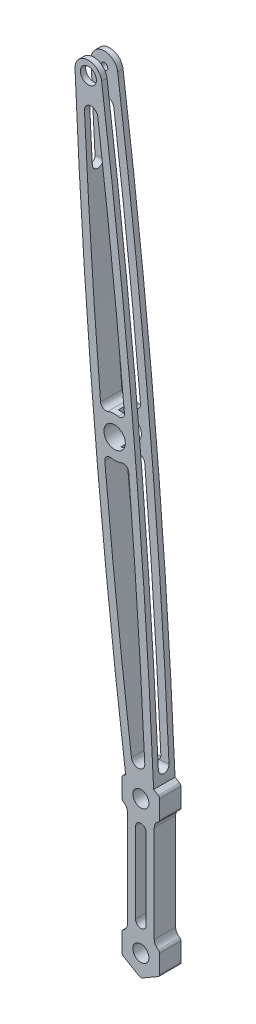
SolidWorks part; units mm, degrees
material "A2017"
ref_plane "正面" through (0, 0, 0) normal (0, 0, 1) x (1, 0, 0)
ref_plane "平面" through (0, 0, 0) normal (0, 1, 0) x (1, 0, 0)
ref_plane "右側面" through (0, 0, 0) normal (1, 0, 0) x (0, 0, -1)
sketch "ｽｹｯﾁ1" plane through (0, 0, 0) normal (0, 0, 1) x (1, 0, 0)
  line L0 (0, 0) -> (9.0749, 0) construction
  line L1 (0, 25) -> (0, 0) construction
  line L2 (0, -16.9171) -> (7, -20.9585)
  line L3 (7, 20.9585) -> (7, 29.0415)
  line L4 (7, 29.0415) -> (0, 33.0829)
  line L5 (0, 33.0829) -> (-7, 29.0415)
  line L6 (-7, 29.0415) -> (-7, 20.9585)
  line L7 (-7, 20.9585) -> (0, 16.9171)
  line L8 (0, 16.9171) -> (7, 20.9585)
  line L9 (-7, -20.9585) -> (0, -16.9171)
  line L10 (-7, -29.0415) -> (-7, -20.9585)
  line L11 (0, -33.0829) -> (-7, -29.0415)
  line L12 (7, -29.0415) -> (0, -33.0829)
  line L13 (7, -20.9585) -> (7, -29.0415)
  circle A0 centre (0, 25) radius 3
  circle A1 centre (0, -25) radius 3
  circle A2 centre (0, 25) radius 7 construction
  circle A3 centre (0, -25) radius 7 construction
  dimension "D1" = 6
  dimension "D2" = 50
  dimension "D3" = 14
extrude "ﾎﾞｽ - 押し出し1" add sketch "ｽｹｯﾁ1" along normal mid plane 8
sketch "ｽｹｯﾁ2" plane through (0, 0, 4) normal (0, 0, 1) x (1, 0, 0)
  line L0 (-7, 20.9585) -> (0, 16.9171) construction
  line L1 (5, -19.8038) -> (-5, -19.8038)
  line L2 (5, -19.8038) -> (5, 19.8038)
  line L3 (5, 19.8038) -> (-5, 19.8038)
  line L4 (-5, -19.8038) -> (-5, 19.8038)
  line L5 (5, -19.8038) -> (-5, 19.8038) construction
  line L6 (5, 19.8038) -> (-5, -19.8038) construction
  point P0 (0, 0)
  dimension "D1" = 10
extrude "ﾎﾞｽ - 押し出し2" add sketch "ｽｹｯﾁ2" against normal up to surface (8 mm away) up to face at (0, 25, -4)
fillet "ﾌｨﾚｯﾄ1" radius 3 4 edges at (5, -19.8038, 0) (-5, 19.8038, 0) (-5, -19.8038, 0) (5, 19.8038, 0)
fillet "ﾌｨﾚｯﾄ2" radius 1 10 edges at (-7, 20.9585, 0) (-7, 29.0415, 0) (0, 33.0829, 0) (7, 29.0415, 0) (7, 20.9585, 0) (7, -29.0415, 0) (0, -33.0829, 0) (-7, -29.0415, 0) (-7, -20.9585, 0) (7, -20.9585, 0)
sketch "ｽｹｯﾁ3" plane through (0, 0, -4) normal (0, 0, -1) x (-1, 0, 0)
  line L0 (0, -15) -> (0, 15) construction
  line L1 (-2, -15) -> (-2, 15)
  line L2 (2, -15) -> (2, 15)
  arc A0 (-2, -15) -> (2, -15) centre (0, -15) ccw
  arc A1 (2, 15) -> (-2, 15) centre (0, 15) ccw
  point P2 (0, 0)
  dimension "D1" = 4
  dimension "D2" = 30
extrude "ｶｯﾄ - 押し出し1" cut sketch "ｽｹｯﾁ3" against normal up to surface (8 mm away) up to face at (0, 0, 4)
sketch "ｽｹｯﾁ5" plane through (0, 0, 4) normal (0, 0, 1) x (1, 0, 0)
  circle A0 centre (0, -25) radius 3 construction
  circle A1 centre (0, 25) radius 3 construction
  circle A2 centre (0, -25) radius 3
  circle A3 centre (0, 25) radius 3
extrude "ﾎﾞｽ - 押し出し3" [suppressed] add sketch "ｽｹｯﾁ5" against normal blind 5
sketch "ｽｹｯﾁ8" plane through (0, 0, -4) normal (0, 0, -1) x (-1, 0, 0)
  circle A0 centre (0, -25) radius 3 construction
  circle A1 centre (0, 25) radius 3 construction
  circle A2 centre (0, -25) radius 3
  circle A3 centre (0, 25) radius 3
extrude "ﾎﾞｽ - 押し出し4" add sketch "ｽｹｯﾁ8" against normal blind 2.5
hole_wizard "M3 すきま穴1" positions "ｽｹｯﾁ6" profile "ｽｹｯﾁ7" hole size "M3" standard "JIS" end condition through all
sketch "ｽｹｯﾁ6" plane through (0, 0, 4) normal (0, 0, -1) x (-1, 0, 0)
  point P0 (0, 25)
  point P3 (0, -25)
sketch "ｽｹｯﾁ7" plane through (0, 25, 4) normal (1, 0, 0) x (0, -1, 0)
  line L0 (0, 0) -> (0, 8)
  line L1 (0, 8) -> (1.7, 8)
  line L2 (1.7, 8) -> (1.7, 0)
  line L5 (1.7, 0) -> (0, 0)
  line L11 (0, -6.35) -> (0, 107.95) construction
  dimension "通し穴の直径" = 3.4
  dimension "通し穴の深さ" = 8
sketch "ｽｹｯﾁ9" plane through (0, 0, 4) normal (0, 0, 1) x (1, 0, 0)
  line L0 (0, 25) -> (0, 298.9535) construction
  line L1 (0, 25) -> (-19.61, 249.1438) construction
  line L2 (0, 25) -> (-19.61, 249.1438) construction
  line L3 (-7.4715, 24.3463) -> (-27.0815, 248.4901) construction
  line L4 (7.4715, 25.6537) -> (-12.1386, 249.7975) construction
  line L15 (-7, 28.4641) -> (-7, 21.5359)
  line L16 (-5, 18.0718) -> (-5, -18.0718)
  line L17 (-7, -21.5359) -> (-7, -28.4641)
  line L18 (-6.5, -29.3301) -> (-0.5, -32.7942)
  line L19 (0.5, -32.7942) -> (6.5, -29.3301)
  line L20 (7, -28.4641) -> (7, -21.5359)
  line L21 (5, -18.0718) -> (5, 18.0718)
  line L22 (7, 21.5359) -> (7, 28.4641)
  line L23 (6.5, 29.3301) -> (0.5, 32.7942)
  line L24 (-0.5, 32.7942) -> (-6.5, 29.3301)
  line L25 (-7, 28.4641) -> (-7, 21.5359)
  line L26 (-5, 18.0718) -> (-5, -18.0718)
  line L27 (-7, -21.5359) -> (-7, -28.4641)
  line L28 (-6.5, -29.3301) -> (-0.5, -32.7942)
  line L29 (0.5, -32.7942) -> (6.5, -29.3301)
  line L30 (7, -28.4641) -> (7, -21.5359)
  line L31 (5, -18.0718) -> (5, 18.0718)
  line L32 (7, 21.5359) -> (7, 28.4641)
  line L33 (6.5, 29.3301) -> (0.5, 32.7942)
  line L34 (-0.5, 32.7942) -> (-6.5, 29.3301)
  arc A0 (-7.4715, 24.3463) -> (7.4715, 25.6537) centre (0, 25) ccw construction
  arc A1 (-12.1386, 249.7975) -> (-27.0815, 248.4901) centre (-19.61, 249.1438) ccw construction
  circle A2 centre (-19.61, 249.1438) radius 5 construction
  circle A3 centre (0, 25) radius 5
  arc A4 (-14.6533, 249.8004) -> (4.9954, 25.2141) centre (-2530.1776, -83.4321) cw
  arc A5 (-24.6055, 248.9297) -> (-4.9567, 24.3434) centre (2510.5676, 357.5759) ccw
  arc A6 (-14.6533, 249.8004) -> (-24.6055, 248.9297) centre (-19.61, 249.1438) ccw
  arc A16 (-7, 21.5359) -> (-6.5, 20.6699) centre (-6, 21.5359) ccw
  arc A17 (-5, 18.0718) -> (-6.5, 20.6699) centre (-8, 18.0718) ccw
  arc A18 (-6.5, -20.6699) -> (-5, -18.0718) centre (-8, -18.0718) ccw
  arc A19 (-6.5, -20.6699) -> (-7, -21.5359) centre (-6, -21.5359) ccw
  arc A20 (-7, -28.4641) -> (-6.5, -29.3301) centre (-6, -28.4641) ccw
  arc A21 (-0.5, -32.7942) -> (0.5, -32.7942) centre (0, -31.9282) ccw
  arc A22 (6.5, -29.3301) -> (7, -28.4641) centre (6, -28.4641) ccw
  arc A23 (7, -21.5359) -> (6.5, -20.6699) centre (6, -21.5359) ccw
  arc A24 (5, -18.0718) -> (6.5, -20.6699) centre (8, -18.0718) ccw
  arc A25 (6.5, 20.6699) -> (5, 18.0718) centre (8, 18.0718) ccw
  arc A26 (6.5, 20.6699) -> (7, 21.5359) centre (6, 21.5359) ccw
  arc A27 (7, 28.4641) -> (6.5, 29.3301) centre (6, 28.4641) ccw
  arc A28 (0.5, 32.7942) -> (-0.5, 32.7942) centre (0, 31.9282) ccw
  arc A29 (-6.5, 29.3301) -> (-7, 28.4641) centre (-6, 28.4641) ccw
  arc A30 (-7, 21.5359) -> (-6.5, 20.6699) centre (-6, 21.5359) ccw
  arc A31 (-5, 18.0718) -> (-6.5, 20.6699) centre (-8, 18.0718) ccw
  arc A32 (-6.5, -20.6699) -> (-5, -18.0718) centre (-8, -18.0718) ccw
  arc A33 (-6.5, -20.6699) -> (-7, -21.5359) centre (-6, -21.5359) ccw
  arc A34 (-7, -28.4641) -> (-6.5, -29.3301) centre (-6, -28.4641) ccw
  arc A35 (-0.5, -32.7942) -> (0.5, -32.7942) centre (0, -31.9282) ccw
  arc A36 (6.5, -29.3301) -> (7, -28.4641) centre (6, -28.4641) ccw
  arc A37 (7, -21.5359) -> (6.5, -20.6699) centre (6, -21.5359) ccw
  arc A38 (5, -18.0718) -> (6.5, -20.6699) centre (8, -18.0718) ccw
  arc A39 (6.5, 20.6699) -> (5, 18.0718) centre (8, 18.0718) ccw
  arc A40 (6.5, 20.6699) -> (7, 21.5359) centre (6, 21.5359) ccw
  arc A41 (7, 28.4641) -> (6.5, 29.3301) centre (6, 28.4641) ccw
  arc A42 (0.5, 32.7942) -> (-0.5, 32.7942) centre (0, 31.9282) ccw
  arc A43 (-6.5, 29.3301) -> (-7, 28.4641) centre (-6, 28.4641) ccw
  point P4 (-9.805, 137.0719)
  arc M28 (0.5, 32.7942) -> (-0.5, 32.7942) centre (0, 31.9282) ccw
  line M29 (-0.5, 32.7942) -> (-6.5, 29.3301)
  dimension "D5" = 10
  dimension "D1" = 5
  dimension "D2" = 225
  dimension "D4" = 15
  dimension "D3" = 0
extrude "ﾎﾞｽ - 押し出し5" add sketch "ｽｹｯﾁ9" against normal up to surface (8 mm away) contours A4 A6 A5 L33 M29 M28 region at (-10.1534, 141.0541, 4) up to face at (1.7, 25, -4)
sketch "ｽｹｯﾁ12" plane through (0, 0, -4) normal (0, 0, -1) x (-1, 0, 0)
  line L0 (19.61, 249.1438) -> (0, 25) construction
hole_wizard "M3 ねじ穴1" positions "ｽｹｯﾁ19" profile "ｽｹｯﾁ20" tap size "M3" standard "JIS" end condition through all
sketch "ｽｹｯﾁ19" plane through (0, 0, 4) normal (0, 0, 1) x (1, 0, 0)
  point P0 (-19.61, 249.1438)
sketch "ｽｹｯﾁ20" plane through (-19.61, 249.1438, 4) normal (1, 0, 0) x (0, -1, 0)
  line L0 (0, 0) -> (0, 8)
  line L1 (0, 8) -> (1.25, 8)
  line L2 (1.25, 8) -> (1.25, 0)
  line L5 (1.25, 0) -> (0, 0)
  line L11 (0, -6.35) -> (0, 107.95) construction
  dimension "次ｻｰﾌｪｽまでのねじ下穴ﾄﾞﾘﾙ直径" = 2.5
  dimension "次ｻｰﾌｪｽまでのねじ下穴ﾄﾞﾘﾙの深さ" = 8
cosmetic thread "穴のねじ山1" parameters "D2"=3
sketch "ｽｹｯﾁ10" plane through (0, 0, 4) normal (0, 0, 1) x (1, 0, 0)
  circle A0 centre (-19.61, 249.1438) radius 3
  point P3 (0, 0)
  point P4 (-19.61, 249.1438)
  dimension "D1" = 6
extrude "ｶｯﾄ - 押し出し2" cut sketch "ｽｹｯﾁ10" against normal blind 6
sketch "ｽｹｯﾁ21" plane through (0, 0, -4) normal (0, 0, -1) x (-1, 0, 0)
  circle A0 centre (19.61, 249.1438) radius 3
  dimension "D1" = 6
extrude "ｶｯﾄ - 押し出し8" [suppressed] cut sketch "ｽｹｯﾁ21" against normal blind 6
ref_plane "平面1" through (2.1706, 0.1899, 0) normal (0.9962, 0.0872, 0) x (0.0872, -0.9962, 0)
sketch "ｽｹｯﾁ13" plane through (0, 0, -4) normal (0, 0, -1) x (-1, 0, 0)
  line L0 (19.61, 249.1438) -> (0, 25) construction
  arc A2 (17.6274, 249.4065) -> (-1.7741, 30.1938) centre (2530.1776, -83.4321) ccw
  arc A3 (17.6274, 249.4065) -> (-1.7741, 30.1938) centre (2530.1776, -83.4321) ccw
  arc A4 (21.0716, 237.1884) -> (16.0946, 237.6238) centre (18.5745, 237.3071) ccw
  arc A5 (2.6995, 30.1943) -> (21.6082, 249.0582) centre (-2510.5676, 357.5759) ccw
  arc A6 (2.6995, 30.1943) -> (21.6082, 249.0582) centre (-2510.5676, 357.5759) ccw
  arc A7 (-1.4616, 36.9554) -> (3.5154, 36.52) centre (1.0356, 36.8367) ccw
  dimension "D3" = 5
  dimension "D1" = 3
  dimension "D2" = 3
extrude "ｶｯﾄ - 押し出し3" cut sketch "ｽｹｯﾁ13" against normal through all contours A3 A7 A6 A4 region at (-9.805, 137.0719, -4)
sketch "ｽｹｯﾁ14" plane through (0, 0, -4) normal (0, 0, -1) x (-1, 0, 0)
  line L0 (14.2879, 136.6797) -> (5.3221, 137.4641) construction
  arc A0 (3.5154, 36.52) -> (21.0716, 237.1884) centre (-2510.5676, 357.5759) ccw construction
  arc A1 (16.0946, 237.6238) -> (-1.4616, 36.9554) centre (2530.1776, -83.4321) ccw construction
  circle A2 centre (9.805, 137.0719) radius 7.5
  arc A3 (5.6744, 29.8068) -> (24.6055, 248.9297) centre (-2510.5676, 357.5759) ccw construction
extrude "ﾎﾞｽ - 押し出し6" add sketch "ｽｹｯﾁ14" against normal up to surface (8 mm away) up to face at (-9.805, 137.0719, 4)
fillet "ﾌｨﾚｯﾄ3" radius 2 4 edges at (-4.8058, 131.481, 0) (-13.7574, 130.6978, 0) (-14.8042, 142.6628, 0) (-5.8526, 143.446, 0)
sketch "ｽｹｯﾁ15" plane through (0, 0, 4) normal (0, 0, 1) x (1, 0, 0)
  line L0 (-19.61, 249.1438) -> (0, 25) construction
  circle A0 centre (-9.805, 137.0719) radius 4
  dimension "D1" = 8
extrude "ｶｯﾄ - 押し出し4" cut sketch "ｽｹｯﾁ15" against normal through all
sketch "ｽｹｯﾁ16" plane through (2.1706, 0.1899, 0) normal (0.9962, 0.0872, 0) x (0.0872, -0.9962, 0)
  line L0 (-254.9049, 0) -> (-34.9049, 0) construction
  line L1 (-254.9049, 4) -> (-254.9049, -4) construction
  line L2 (-254.9049, 2) -> (-34.9049, 2)
  line L3 (-254.9049, -2) -> (-34.9049, -2)
  arc A0 (-254.9049, 2) -> (-254.9049, -2) centre (-254.9049, 0) ccw
  arc A1 (-34.9049, -2) -> (-34.9049, 2) centre (-34.9049, 0) ccw
  point P5 (-144.9049, 0)
  dimension "D1" = 4
  dimension "D2" = 220
extrude "ｶｯﾄ - 押し出し6" cut sketch "ｽｹｯﾁ16" along normal through all
sketch "ｽｹｯﾁ22" plane through (2.1706, 0.1899, 0) normal (0.9962, 0.0872, 0) x (0, 0, -1)
  line L0 (0, 254.9049) -> (0, 219.9049) construction
  line L1 (-2, 254.9049) -> (2, 254.9049) construction
  line L2 (2, 254.9049) -> (2, 219.9049)
  line L3 (-2, 254.9049) -> (-2, 219.9049)
  line L4 (2, 252.9049) -> (2, 254.9049) construction
  arc A0 (2, 254.9049) -> (-2, 254.9049) centre (0, 254.9049) ccw
  arc A1 (-2, 219.9049) -> (2, 219.9049) centre (0, 219.9049) ccw
  point P5 (0, 237.4049)
  dimension "D1" = 35
extrude "ｶｯﾄ - 押し出し9" cut sketch "ｽｹｯﾁ22" against normal through all
